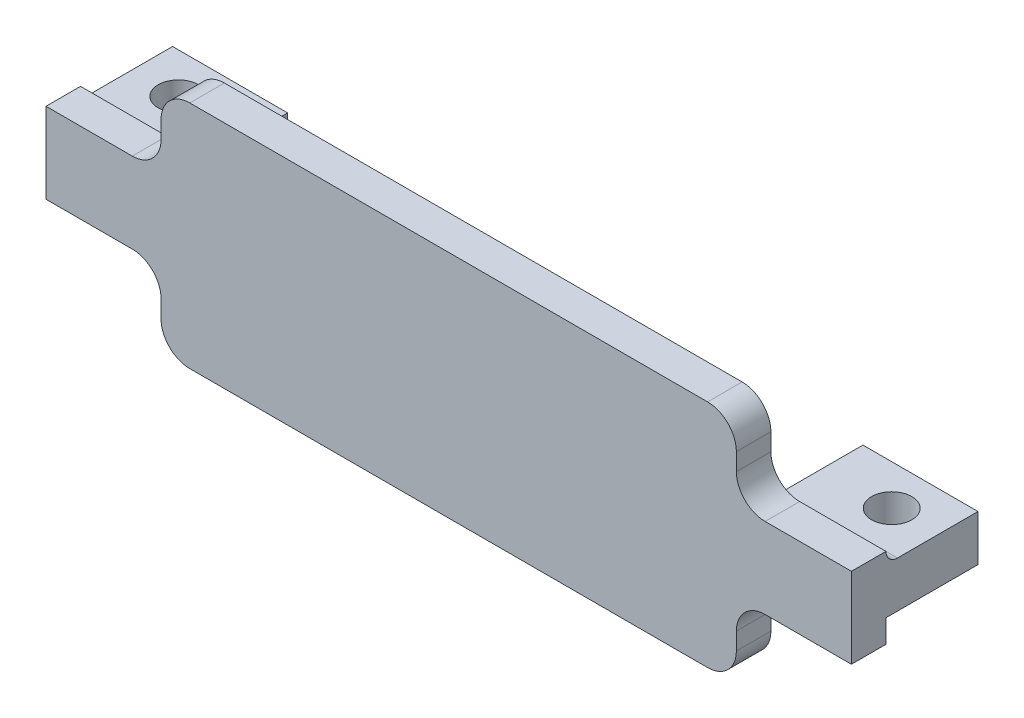
SolidWorks part; units mm, degrees
ref_plane "Front Plane" through (0, 0, 0) normal (0, 0, 1) x (1, 0, 0)
ref_plane "Top Plane" through (0, 0, 0) normal (0, 1, 0) x (1, 0, 0)
ref_plane "Right Plane" through (0, 0, 0) normal (1, 0, 0) x (0, 0, -1)
sketch "Sketch1" plane through (0, 0, 0) normal (0, 0, 1) x (1, 0, 0)
  line L1 (10, 77.5) -> (-10, 77.5)
  line L2 (10, 77.5) -> (10, -77.5)
  line L3 (10, -77.5) -> (-10, -77.5)
  line L4 (-10, 77.5) -> (-10, -77.5)
  line L5 (10, 77.5) -> (-10, -77.5) construction
  line L6 (10, -77.5) -> (-10, 77.5) construction
  point P0 (0, 0)
  dimension "D1" = 20
  dimension "D2" = 155
extrude "Boss-Extrude1" add sketch "Sketch1" along normal blind 4
sketch "Sketch2" plane through (0, 0, 4) normal (0, 0, 1) x (1, 0, 0)
  line L0 (10, -77.5) -> (10, 77.5) construction
  line L1 (-10, -77.5) -> (10, -77.5)
  line L2 (-10, -77.5) -> (-10, -73.5)
  line L3 (-10, -73.5) -> (10, -73.5)
  line L4 (10, -77.5) -> (10, -73.5)
  dimension "D1" = 4
extrude "Boss-Extrude3" add sketch "Sketch2" along normal blind 50 contours L3 L4 L1 L2
sketch "Sketch7" plane through (0, 0, 0) normal (1, 0, 0) x (0, 0, -1)
  line L0 (-29, -73.5) -> (-4, 21.5)
  line L1 (-54, -73.5) -> (-4, -73.5) construction
  line L2 (-4, -73.5) -> (-4, 77.5) construction
  dimension "D1" = 95
  dimension "D2" = 25
rib "Rib2" sketch "Sketch7" sketch "Sketch7" thickness 4 extrusion direction parallel to sketch draft on no parameters "D1"=4
sketch "Sketch8" plane through (0, 0, 4) normal (0, 0, 1) x (1, 0, 0)
  line L0 (-10, 77.5) -> (-10, -73.5) construction
  line L1 (10, 77.5) -> (-10, 77.5)
  line L2 (10, 77.5) -> (10, 74.5)
  line L3 (10, 74.5) -> (-10, 74.5)
  line L4 (-10, 77.5) -> (-10, 74.5)
  dimension "D1" = 3
extrude "Boss-Extrude4" add sketch "Sketch8" along normal blind 3.5
sketch "Sketch9" plane through (0, 0, 7.5) normal (0, 0, 1) x (1, 0, 0)
  line L1 (-35, 79.5) -> (35, 79.5)
  line L2 (-35, 79.5) -> (-35, 74.5)
  line L3 (-35, 74.5) -> (35, 74.5)
  line L4 (35, 79.5) -> (35, 74.5)
  line L5 (10, -73.5) -> (10, 74.5) construction
  line L7 (-10, 74.5) -> (10, 74.5) construction
  dimension "D1" = 70
  dimension "D2" = 25
  dimension "D3" = 5
extrude "Boss-Extrude6" add sketch "Sketch9" along normal blind 3
sketch "Sketch10" plane through (0, 0, 7.5) normal (0, 0, -1) x (-1, 0, 0)
  line L1 (35, 74.5) -> (25, 74.5)
  line L2 (35, 74.5) -> (35, 78.5)
  line L3 (35, 78.5) -> (25, 78.5)
  line L4 (25, 74.5) -> (25, 78.5)
  line L5 (-35, 74.5) -> (-25, 74.5)
  line L6 (-35, 74.5) -> (-35, 78.5)
  line L7 (-35, 78.5) -> (-25, 78.5)
  line L8 (-25, 74.5) -> (-25, 78.5)
  dimension "D1" = 10
  dimension "D2" = 4
extrude "Boss-Extrude7" add sketch "Sketch10" along normal blind 8
sketch "Sketch12" plane through (0, 78.5, 0) normal (0, 1, 0) x (1, 0, 0)
  line L1 (-35, -7.5) -> (-25, -7.5) construction
  line L2 (-35, 0.5) -> (-35, -7.5) construction
  line L3 (35, -7.5) -> (-35, -7.5) construction
  line L4 (35, 0.5) -> (35, -7.5) construction
  circle A0 centre (-31, -3) radius 1.75
  circle A1 centre (31, -3) radius 1.75
  dimension "D1" = 3.5
  dimension "D4" = 3.5
  dimension "D2" = 4.5
  dimension "D3" = 4
  dimension "D5" = 4.5
  dimension "D6" = 4
extrude "Cut-Extrude1" cut sketch "Sketch12" against normal blind 10
sketch "Sketch13" plane through (0, -77.5, 0) normal (0, -1, 0) x (1, 0, 0)
  line L1 (58.3124, -29.3972) -> (-53.0067, -29.3972)
  line L2 (58.3124, -29.3972) -> (58.3124, 70.3466)
  line L3 (58.3124, 70.3466) -> (-53.0067, 70.3466)
  line L4 (-53.0067, -29.3972) -> (-53.0067, 70.3466)
  point P4 (-53.0067, 70.3466)
extrude "Cut-Extrude2" cut sketch "Sketch13" against normal up to surface (152 mm away) up to face at (-31, 74.5, 4.75)
sketch "Sketch14" plane through (0, 79.5, 0) normal (0, 1, 0) x (1, 0, 0)
  line L0 (35, -10.5) -> (-35, -10.5) construction
  line L1 (-25, -10.5) -> (25, -10.5)
  line L2 (-25, -10.5) -> (-25, -7.5)
  line L3 (-25, -7.5) -> (25, -7.5)
  line L4 (25, -10.5) -> (25, -7.5)
  line L5 (-25, 0.5) -> (-25, -7.5) construction
  line L6 (25, 0.5) -> (25, -7.5) construction
  point P6 (-23.1029, -10.5)
extrude "Boss-Extrude8" add sketch "Sketch14" along normal blind 6.5
ref_plane "Plane1" through (0, 76, 0) normal (0, -1, 0) x (-1, 0, 0)
mirror "Mirror1" about plane through (0, 76, 0) normal (0, -1, 0) of "Boss-Extrude6", "Boss-Extrude8"
fillet "Fillet1" radius 1 7 edges at (30, 78.5, 7.5) (-30, 78.5, 7.5) (10, 76, 7.5) (-10, 76, 7.5) (0, 77.5, 7.5) (25, 76.5, 7.5) (-25, 76.5, 7.5)
fillet "Fillet2" radius 2.5 8 edges at (-25, 86, 9) (-25, 66, 9) (25, 66, 9) (25, 86, 9) (-25, 72.5, 9) (-25, 79.5, 9) (25, 72.5, 9) (25, 79.5, 9)
